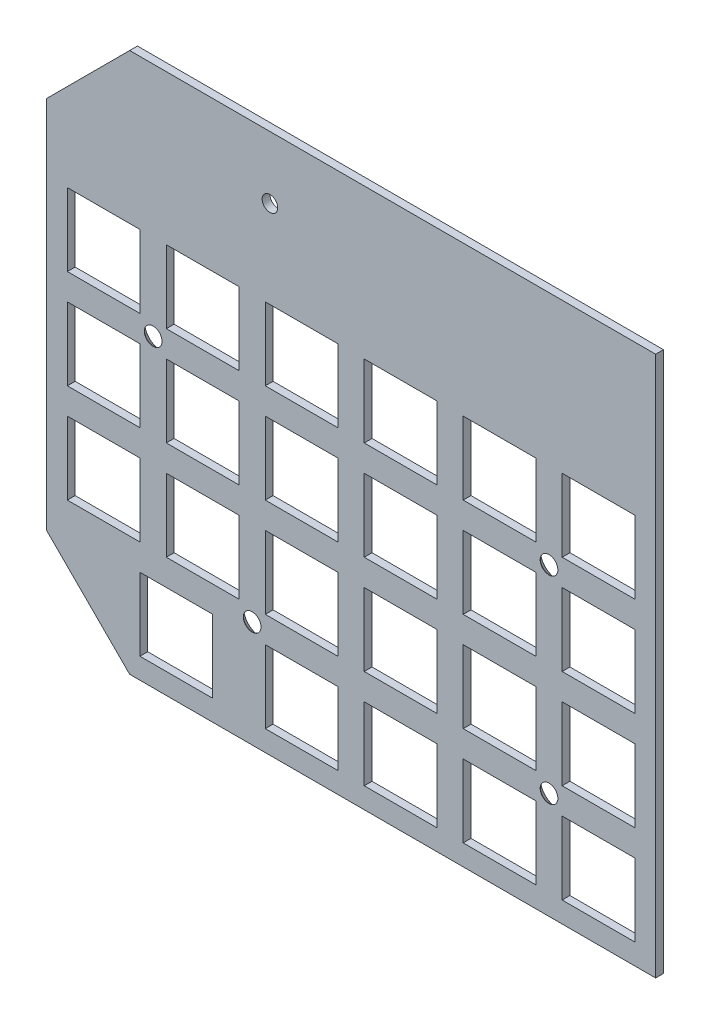
SolidWorks part; units mm, degrees
material "Alliage 1060"
ref_plane "Plan de face" through (0, 0, 0) normal (0, 0, 1) x (1, 0, 0)
ref_plane "Plan de dessus" through (0, 0, 0) normal (0, 1, 0) x (1, 0, 0)
ref_plane "Plan de droite" through (0, 0, 0) normal (1, 0, 0) x (0, 0, -1)
sketch "Esquisse1" plane through (0, 0, 0) normal (0, 0, 1) x (1, 0, 0)
  line L0 (0, -85) -> (16, -101)
  line L4 (117.25, 3) -> (117.25, -101)
  line L5 (16, 3) -> (0, -13)
  line L7 (117.25, 3) -> (16, 3)
  line L8 (0, -13) -> (0, -85)
  line L9 (16, -101) -> (117.25, -101)
  dimension "D1" = 104
  dimension "D2" = 117.25
  dimension "D3" = 16
  dimension "D4" = 16
  dimension "D5" = 16
  dimension "D6" = 16
extrude "Boss.-Extru.1" add sketch "Esquisse1" along normal blind 1.5
sketch "Esquisse3" plane through (0, 0, 0) normal (0, 0, -1) x (-1, 0, 0)
  line L0 (-94.2, -25.85) -> (-94.2, -39.85)
  line L1 (-113.25, -25.85) -> (-99.25, -25.85)
  line L2 (-113.25, -25.85) -> (-113.25, -39.85)
  line L3 (-113.25, -39.85) -> (-99.25, -39.85)
  line L4 (-99.25, -25.85) -> (-99.25, -39.85)
  line L5 (-106.25, -39.85) -> (-106.25, -25.85) construction
  line L6 (-113.25, -32.85) -> (-99.25, -32.85) construction
  line L7 (-94.2, -25.85) -> (-80.2, -25.85)
  line L8 (-80.2, -25.85) -> (-80.2, -39.85)
  line L9 (-94.2, -39.85) -> (-80.2, -39.85)
  line L10 (-75.15, -25.85) -> (-75.15, -39.85)
  line L11 (-75.15, -25.85) -> (-61.15, -25.85)
  line L12 (-61.15, -25.85) -> (-61.15, -39.85)
  line L13 (-75.15, -39.85) -> (-61.15, -39.85)
  line L14 (-56.1, -25.85) -> (-56.1, -39.85)
  line L15 (-56.1, -25.85) -> (-42.1, -25.85)
  line L16 (-42.1, -25.85) -> (-42.1, -39.85)
  line L17 (-56.1, -39.85) -> (-42.1, -39.85)
  line L18 (-37.05, -25.85) -> (-37.05, -39.85)
  line L19 (-37.05, -25.85) -> (-23.05, -25.85)
  line L20 (-23.05, -25.85) -> (-23.05, -39.85)
  line L21 (-37.05, -39.85) -> (-23.05, -39.85)
  line L22 (-18, -25.85) -> (-18, -39.85)
  line L23 (-18, -25.85) -> (-4, -25.85)
  line L24 (-4, -25.85) -> (-4, -39.85)
  line L25 (-18, -39.85) -> (-4, -39.85)
  line L26 (-94.2, -44.9) -> (-94.2, -58.9)
  line L27 (-94.2, -44.9) -> (-80.2, -44.9)
  line L28 (-80.2, -44.9) -> (-80.2, -58.9)
  line L29 (-94.2, -58.9) -> (-80.2, -58.9)
  line L30 (-75.15, -44.9) -> (-75.15, -58.9)
  line L31 (-75.15, -44.9) -> (-61.15, -44.9)
  line L32 (-61.15, -44.9) -> (-61.15, -58.9)
  line L33 (-75.15, -58.9) -> (-61.15, -58.9)
  line L34 (-56.1, -44.9) -> (-56.1, -58.9)
  line L35 (-56.1, -44.9) -> (-42.1, -44.9)
  line L36 (-42.1, -44.9) -> (-42.1, -58.9)
  line L37 (-56.1, -58.9) -> (-42.1, -58.9)
  line L38 (-37.05, -44.9) -> (-37.05, -58.9)
  line L39 (-37.05, -44.9) -> (-23.05, -44.9)
  line L40 (-23.05, -44.9) -> (-23.05, -58.9)
  line L41 (-37.05, -58.9) -> (-23.05, -58.9)
  line L42 (-18, -44.9) -> (-18, -58.9)
  line L43 (-18, -44.9) -> (-4, -44.9)
  line L44 (-4, -44.9) -> (-4, -58.9)
  line L45 (-18, -58.9) -> (-4, -58.9)
  line L46 (-94.2, -63.95) -> (-94.2, -77.95)
  line L47 (-94.2, -63.95) -> (-80.2, -63.95)
  line L48 (-80.2, -63.95) -> (-80.2, -77.95)
  line L49 (-94.2, -77.95) -> (-80.2, -77.95)
  line L50 (-75.15, -63.95) -> (-75.15, -77.95)
  line L51 (-75.15, -63.95) -> (-61.15, -63.95)
  line L52 (-61.15, -63.95) -> (-61.15, -77.95)
  line L53 (-75.15, -77.95) -> (-61.15, -77.95)
  line L54 (-56.1, -63.95) -> (-56.1, -77.95)
  line L55 (-56.1, -63.95) -> (-42.1, -63.95)
  line L56 (-42.1, -63.95) -> (-42.1, -77.95)
  line L57 (-56.1, -77.95) -> (-42.1, -77.95)
  line L58 (-37.05, -63.95) -> (-37.05, -77.95)
  line L59 (-37.05, -63.95) -> (-23.05, -63.95)
  line L60 (-23.05, -63.95) -> (-23.05, -77.95)
  line L61 (-37.05, -77.95) -> (-23.05, -77.95)
  line L62 (-18, -63.95) -> (-18, -77.95)
  line L63 (-18, -63.95) -> (-4, -63.95)
  line L64 (-4, -63.95) -> (-4, -77.95)
  line L65 (-18, -77.95) -> (-4, -77.95)
  line L66 (-94.2, -83) -> (-94.2, -97)
  line L67 (-94.2, -83) -> (-80.2, -83)
  line L68 (-80.2, -83) -> (-80.2, -97)
  line L69 (-94.2, -97) -> (-80.2, -97)
  line L70 (-75.15, -83) -> (-75.15, -97)
  line L71 (-75.15, -83) -> (-61.15, -83)
  line L72 (-61.15, -83) -> (-61.15, -97)
  line L73 (-75.15, -97) -> (-61.15, -97)
  line L74 (-56.1, -83) -> (-56.1, -97)
  line L75 (-56.1, -83) -> (-42.1, -83)
  line L76 (-42.1, -83) -> (-42.1, -97)
  line L77 (-56.1, -97) -> (-42.1, -97)
  line L86 (-113.25, -44.9) -> (-113.25, -58.9)
  line L87 (-113.25, -44.9) -> (-99.25, -44.9)
  line L88 (-99.25, -44.9) -> (-99.25, -58.9)
  line L89 (-113.25, -58.9) -> (-99.25, -58.9)
  line L90 (-113.25, -63.95) -> (-113.25, -77.95)
  line L91 (-113.25, -63.95) -> (-99.25, -63.95)
  line L92 (-99.25, -63.95) -> (-99.25, -77.95)
  line L93 (-113.25, -77.95) -> (-99.25, -77.95)
  line L94 (-113.25, -83) -> (-113.25, -97)
  line L95 (-113.25, -83) -> (-99.25, -83)
  line L96 (-99.25, -83) -> (-99.25, -97)
  line L97 (-113.25, -97) -> (-99.25, -97)
  line L98 (-4, -83) -> (-4, -97) [skipped]
  line L99 (-18, -97) -> (-4, -97) [skipped]
  line L100 (-18, -83) -> (-18, -97) [skipped]
  line L101 (-18, -83) -> (-4, -83) [skipped]
  line L103 (-117.25, -101) -> (-117.25, 3) construction
  line L104 (-16, -101) -> (-117.25, -101) construction
  line L107 (-37.05, -83) -> (-23.05, -83) [skipped]
  line L108 (-23.05, -83) -> (-23.05, -97) [skipped]
  line L109 (-37.05, -83) -> (-37.05, -97) [skipped]
  line L110 (-37.05, -97) -> (-23.05, -97) [skipped]
  line L111 (0, -13) -> (0, -85) construction
  line L112 (-31.97, -83) -> (-17.97, -83)
  line L113 (-31.97, -83) -> (-31.97, -97)
  line L114 (-31.97, -97) -> (-17.97, -97)
  line L115 (-17.97, -83) -> (-17.97, -97)
  line L116 (-24.97, -97) -> (-24.97, -83) construction
  line L117 (-31.97, -90) -> (-17.97, -90) construction
  line L122 (-117.25, 3) -> (-16, 3) construction
  circle A5 centre (-43, -9) radius 1.5
  point P0 (-106.25, -32.85)
  point P84 (-24.97, -90)
  dimension "D7" = 43
  dimension "D8" = 12
  dimension "D1" = 14
  dimension "D2" = 14
  dimension "D5" = 4
  dimension "D6" = 4
  dimension "D9" = 5.05
  dimension "D10" = 14
  dimension "D11" = 14
  dimension "D12" = 10.13
  dimension "D13" = 5.05
  dimension "D3" = 6
  dimension "D4" = 4
extrude "Enlèv. mat.-Extru.2" cut sketch "Esquisse3" against normal blind 10
sketch "Esquisse4" plane through (0, 0, 0) normal (0, 0, -1) x (-1, 0, 0)
  line L0 (-99.25, -39.85) -> (-94.2, -44.9) construction
  line L1 (-23.05, -39.85) -> (-18, -44.9) construction
  line L2 (-37.05, -77.95) -> (-42.1, -83) construction
  line L3 (-94.2, -77.95) -> (-99.25, -83) construction
  point P16 (-96.725, -42.375)
  point P17 (-96.725, -80.475)
  point P18 (-39.575, -80.475)
hole_wizard "Fraisage pour vis à tête fraisée M31" positions "Esquisse5" profile "Esquisse6" countersink size "M3" standard "Ansi Metric" end condition through all
sketch "Esquisse5" plane through (0, 0, 0) normal (0, 0, -1) x (-1, 0, 0)
  line L0 (-23.05, -39.85) -> (-18, -44.9) construction
  line L1 (-37.05, -77.95) -> (-42.1, -83) construction
  point P0 (-96.725, -42.375)
  point P3 (-96.725, -80.475)
  point P6 (-20.525, -42.375)
  point P10 (-39.575, -80.475)
sketch "Esquisse6" plane through (96.725, -42.375, 0) normal (1, 0, 0) x (0, 1, 0)
  line L0 (0, 0) -> (0, 1.5)
  line L1 (0, 1.5) -> (1.7, 1.5)
  line L2 (1.7, 1.5) -> (1.7, 1.45)
  line L3 (1.7, 1.45) -> (3.15, 0)
  line L5 (3.15, 0) -> (0, 0)
  line L6 (-1.7, 1.45) -> (-3.15, 0) construction
  line L11 (0, -6.35) -> (0, 107.95) construction
  dimension "Diamètre du perçage jusqu'au prochain" = 3.4
  dimension "Profondeur du perçage jusqu'au prochain" = 1.5
  dimension "Diamètre du fraisage entrant" = 6.3
  dimension "Angle du fraisage entrant" = 90
